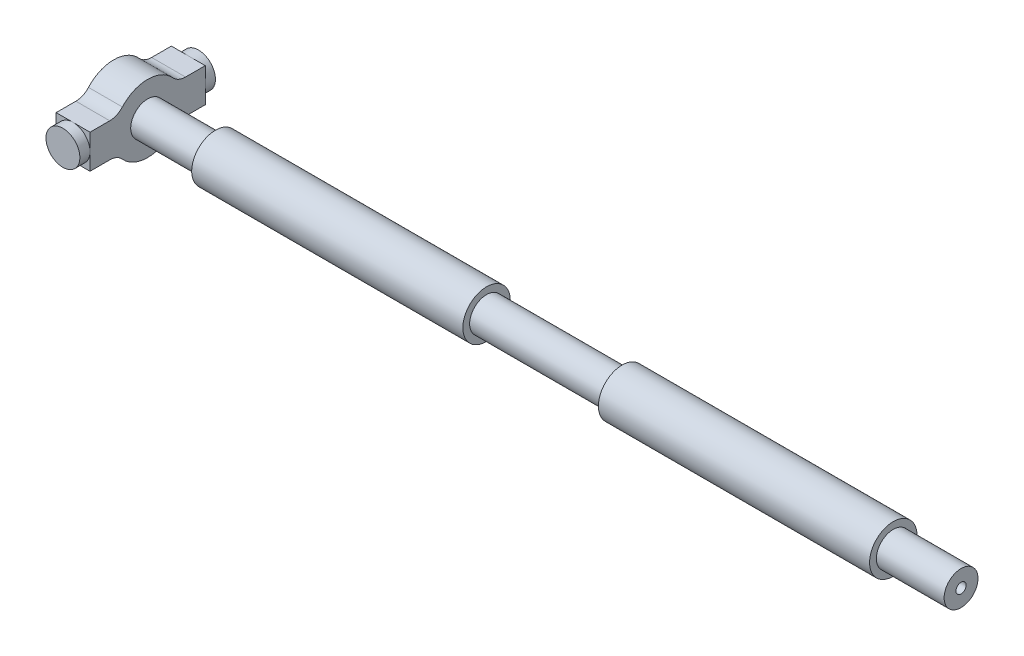
SolidWorks part; units mm, degrees
ref_plane "Front Plane" through (0, 0, 0) normal (0, 0, 1) x (1, 0, 0)
ref_plane "Top Plane" through (0, 0, 0) normal (0, 1, 0) x (1, 0, 0)
ref_plane "Right Plane" through (0, 0, 0) normal (1, 0, 0) x (0, 0, -1)
sketch "Primary Tube Sketch" plane through (0, 0, 0) normal (1, 0, 0) x (0, 0, -1)
  circle A1 centre (0, 0) radius 5
  dimension "D2" = 10
extrude "Primary Tube Extrude" add sketch "Primary Tube Sketch" along normal blind 250
sketch "Thick Tube Sketch" plane through (250, 0, 0) normal (1, 0, 0) x (0, 0, -1)
  circle A0 centre (0, 0) radius 7
  circle A1 centre (0, 0) radius 5 construction
  dimension "D1" = 2
extrude "Thick Tube Extrude 1" add sketch "Thick Tube Sketch" against normal blind 80 from offset 20 offset against normal yes
extrude "Thick Tube Extrude 2" add sketch "Sketch1<2>" against normal blind 80 from offset 140 offset against normal yes
sketch "Sketch1<2>" plane through (250, 0, 0) normal (1, 0, 0) x (0, 0, -1) same geometry as "Thick Tube Sketch"
sketch "Plunger Sketch" plane through (250, 0, 0) normal (1, 0, 0) x (0, 0, -1)
  circle A0 centre (0, 0) radius 1.5
  dimension "D1" = 3
extrude "Plunger Cut" cut sketch "Plunger Sketch" against normal blind 100
sketch "T Support Sketch" plane through (0, 0, 0) normal (-1, 0, 0) x (0, 0, 1)
  line L0 (8.6603, 5) -> (17, 5)
  line L1 (-17, 5) -> (-8.6603, 5)
  line L2 (-17, 5) -> (-17, -5)
  line L3 (-17, -5) -> (-8.6603, -5)
  line L4 (17, 5) -> (17, -5)
  line L5 (-17, 5) -> (17, -5) construction
  line L6 (-17, -5) -> (17, 5) construction
  line L7 (8.6603, -5) -> (17, -5)
  circle A0 centre (0, 0) radius 5 construction
  arc A1 (-8.6603, -5) -> (8.6603, -5) centre (0, 0) ccw
  arc A2 (8.6603, 5) -> (-8.6603, 5) centre (0, 0) ccw
  point P0 (0, 0)
  dimension "D2" = 20
  dimension "D1" = 34
extrude "T Support Extrude" add sketch "T Support Sketch" against normal blind 10 separate body
fillet "T Support Fillet" radius 5 4 edges at (5, -5, 8.6603) (5, -5, -8.6603) (5, 5, 8.6603) (5, 5, -8.6603)
sketch "Arm Pin Sketch" plane through (0, 0, 17) normal (0, 0, 1) x (1, 0, 0)
  line L0 (10, 5) -> (0, 5) construction
  line L1 (0, -5) -> (0, 5) construction
  circle A0 centre (5, 0) radius 5
  dimension "D1" = 10
extrude "Arm Pin Extrude 1" add sketch "Arm Pin Sketch" along normal blind 3 separate body
extrude "Arm Pin Extrude 2" add sketch "Arm Pin Sketch<2>" against normal blind 3 from surface separate body starting at face at (5, 0, -17)
sketch "Arm Pin Sketch<2>" plane through (0, 0, 17) normal (0, 0, 1) x (1, 0, 0) same geometry as "Arm Pin Sketch"
